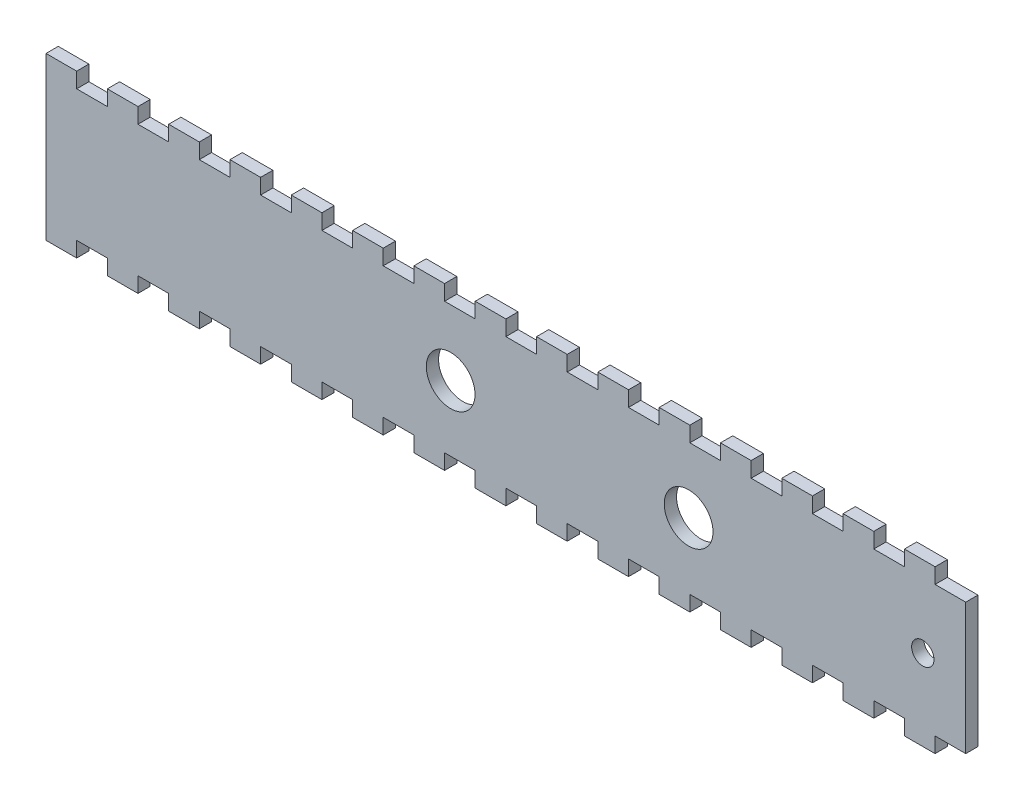
SolidWorks part; units mm, degrees
ref_plane "Front Plane" through (0, 0, 0) normal (0, 0, 1) x (1, 0, 0)
ref_plane "Top Plane" through (0, 0, 0) normal (0, 1, 0) x (1, 0, 0)
ref_plane "Right Plane" through (0, 0, 0) normal (1, 0, 0) x (0, 0, -1)
sketch "Sketch1" plane through (0, 0, 0) normal (0, 0, 1) x (1, 0, 0)
  line L0 (0, 10.7) -> (150, 10.7) construction
  line L1 (0, 0) -> (150, 0)
  line L2 (0, 0) -> (0, 21.4)
  line L3 (0, 21.4) -> (150, 21.4)
  line L4 (150, 0) -> (150, 21.4)
  circle A0 centre (65.995, 10.7) radius 3.975
  circle A1 centre (104.805, 10.7) radius 3.975
  circle A2 centre (143, 10.7) radius 1.825
  dimension "D3" = 7.95
  dimension "D4" = 7.95
  dimension "D12" = 45.195
  dimension "D13" = 7
  dimension "D14" = 3.65
extrude "Boss-Extrude2" add sketch "Sketch1" along normal blind 2 contours L2 L0 A0 A1 L4 L3 | L0 L2 L1 L4 A1 A0 region at (74.4375, 16.1827, 0) region at (74.4375, 5.2173, 0)
sketch "Sketch2" plane through (0, 21.4, 0) normal (0, 1, 0) x (1, 0, 0)
  line L0 (0, -2) -> (150, -2) construction
  line L1 (0, 0) -> (5, 0)
  line L2 (0, 0) -> (0, -2)
  line L3 (0, -2) -> (5, -2)
  line L4 (5, 0) -> (5, -2)
  dimension "D1" = 5
extrude "Boss-Extrude3" add sketch "Sketch2" along normal blind 2.5
pattern_linear "LPattern1" count 15 spacing 10 along (1, 0, 0) of "Boss-Extrude3"
sketch "Sketch3" plane through (0, 0, 0) normal (0, -1, 0) x (-1, 0, 0)
  line L0 (0, -2) -> (-150, -2) construction
  line L1 (0, 0) -> (-5, 0)
  line L2 (0, 0) -> (0, -2)
  line L3 (0, -2) -> (-5, -2)
  line L4 (-5, 0) -> (-5, -2)
  dimension "D1" = 5
extrude "Boss-Extrude4" add sketch "Sketch3" along normal blind 2.5
pattern_linear "LPattern2" count 15 spacing 10 along (1, 0, 0) of "Boss-Extrude4"
